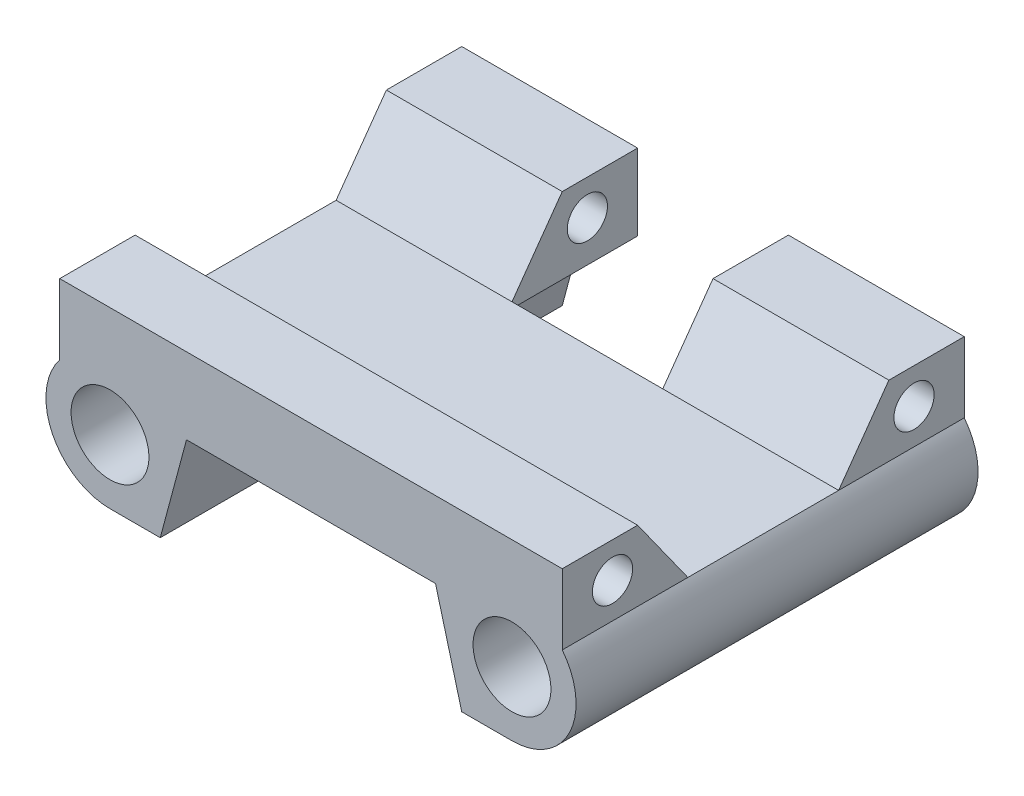
SolidWorks part; units mm, degrees
material "ABS"
ref_plane "Plano frontal" through (0, 0, 0) normal (0, 0, 1) x (1, 0, 0)
ref_plane "Plano superior" through (0, 0, 0) normal (0, 1, 0) x (1, 0, 0)
ref_plane "Plano direito" through (0, 0, 0) normal (1, 0, 0) x (0, 0, -1)
sketch "Esboço1" plane through (0, 0, 0) normal (0, 0, 1) x (1, 0, 0)
  line L0 (-63.5982, -1.8406) -> (63.0213, -1.8406) construction
  line L1 (-63.5982, 6.1594) -> (-63.5982, -1.8406) construction
  line L2 (-40, -25.499) -> (-30, -25.499)
  line L3 (-30, -25.499) -> (-24.7752, -6)
  line L4 (-50, -4.8406) -> (-50, 9.1594)
  line L5 (-50, 9.1594) -> (50, 9.1594)
  line L6 (0, 0) -> (0, -46.1263) construction
  line L7 (50, 9.1594) -> (50, -4.8406)
  line L8 (30, -25.499) -> (24.7752, -6)
  line L9 (40, -25.499) -> (30, -25.499)
  line L11 (-24.7752, -6) -> (24.7752, -6)
  line L12 (-40, -12.7495) -> (40, -12.7495) construction
  line L13 (-63.5982, 6.1594) -> (63.0213, 6.1594) construction
  circle A0 centre (-40, -12.7495) radius 7.75
  circle A1 centre (40, -12.7495) radius 7.75
  arc A2 (40, -25.499) -> (50, -4.8406) centre (40, -12.7495) ccw
  arc A3 (-50, -4.8406) -> (-40, -25.499) centre (-40, -12.7495) ccw
  point P14 (-63.5982, 2.1594)
  point P15 (-50, 2.1594)
  point P17 (0, -12.2866)
  point P24 (40, 0)
  point P27 (-40, 0)
  dimension "D1" = 15.5
  dimension "D7" = 14
  dimension "D10" = 12.7495
  dimension "D2" = 100
  dimension "D3" = 75
  dimension "D4" = 10
  dimension "D5" = 6.7495
  dimension "D6" = 40
  dimension "D8" = 6
  dimension "D11" = 8
extrude "Ressalto-extrusão1" add sketch "Esboço1" along normal blind 80
sketch "Esboço4" plane through (-50, 0, 0) normal (-1, 0, 0) x (0, 0, 1)
  line L0 (10, 2.1594) -> (70, 2.1594) construction
  line L1 (80, -4.8406) -> (0, -4.8406) construction
  line L3 (80, 9.1594) -> (0, 9.1594) construction
  line L4 (15, 9.1594) -> (25, -4.8406)
  line L5 (25, -4.8406) -> (55, -4.8406)
  line L7 (55, -4.8406) -> (65, 9.1594)
  line L8 (65, 9.1594) -> (15, 9.1594)
  line L9 (0, 9.1594) -> (0, -4.8406) construction
  circle A0 centre (10, 2.1594) radius 4
  circle A1 centre (70, 2.1594) radius 4
  point P6 (40, 2.1594)
  point P9 (40, 9.1594)
  point P12 (40, -4.8406)
  point P17 (40, 9.1594)
  point P22 (0, 2.1594)
  dimension "D2" = 8
  dimension "D1" = 60
  dimension "D4" = 30
  dimension "D5" = 50
extrude "Corte-extrusão3" cut sketch "Esboço4" against normal through all both and the other way through all
sketch "Esboço2" plane through (0, -25.499, 0) normal (0, -1, 0) x (1, 0, 0)
  line L1 (-52.7495, 40) -> (52.7495, 40) construction
  line L2 (-52.7495, 80) -> (-52.7495, 0) construction
  line L3 (52.7495, 0) -> (52.7495, 80) construction
  line L6 (0, 0) -> (0, 80) construction
  line L7 (-24.7752, 80) -> (24.7752, 80) construction
  line L9 (-24.7752, 0) -> (24.7752, 0) construction
  line L10 (-15, 25) -> (15, 25)
  line L11 (-15, 25) -> (-15, 0)
  line L12 (-15, 0) -> (15, 0)
  line L13 (15, 25) -> (15, 0)
  line L14 (-15, 25) -> (15, 0) construction
  line L15 (-15, 0) -> (15, 25) construction
  point P20 (0, 12.5)
  dimension "D4" = 25
  dimension "D5" = 30
extrude "Corte-extrusão1" cut sketch "Esboço2" against normal through all
